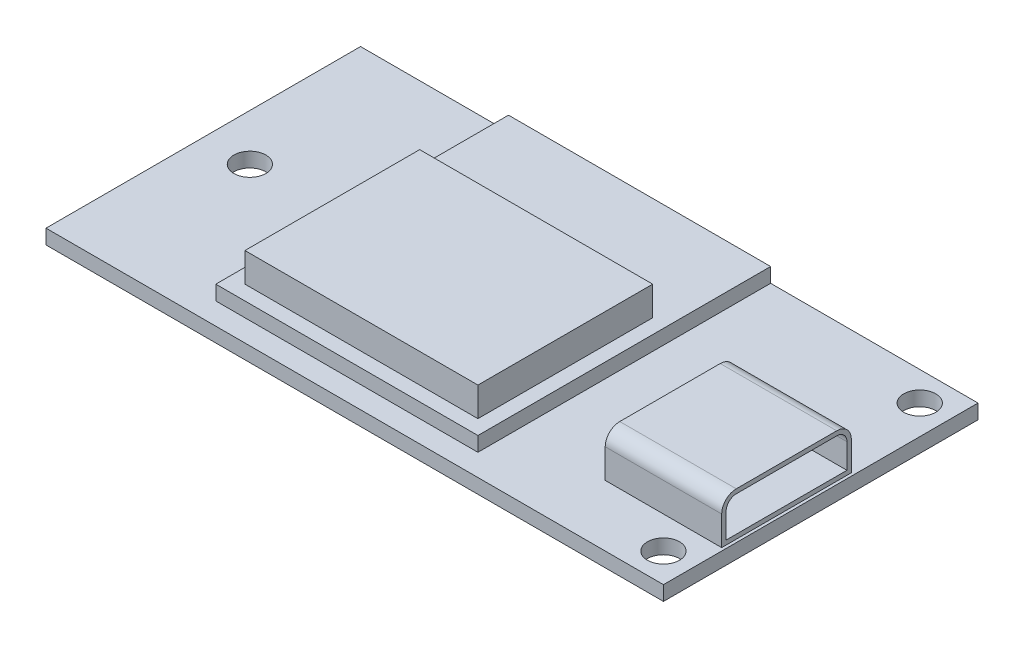
SolidWorks part; units mm, degrees
ref_plane "前视基准面" through (0, 0, 0) normal (0, 0, 1) x (1, 0, 0)
ref_plane "上视基准面" through (0, 0, 0) normal (0, 1, 0) x (1, 0, 0)
ref_plane "右视基准面" through (0, 0, 0) normal (1, 0, 0) x (0, 0, -1)
sketch "草图1" plane through (0, 0, 0) normal (0, 1, 0) x (1, 0, 0)
  line L1 (-21.2, 10.8) -> (21.2, 10.8)
  line L2 (-21.2, 10.8) -> (-21.2, -10.8)
  line L3 (-21.2, -10.8) -> (21.2, -10.8)
  line L4 (21.2, 10.8) -> (21.2, -10.8)
  line L5 (-21.2, 10.8) -> (21.2, -10.8) construction
  line L6 (-21.2, -10.8) -> (21.2, 10.8) construction
  circle A0 centre (-18, 0) radius 1.1
  circle A1 centre (19.2, 8.8) radius 1.1
  circle A2 centre (19.2, -8.8) radius 1.1
  point P0 (0, 0)
  dimension "D5" = 2.2
  dimension "D8" = 2.2
  dimension "D11" = 2.2
  dimension "D2" = 17.6
  dimension "D3" = 3.2
  dimension "D4" = 10.8
  dimension "D6" = 2
  dimension "D7" = 2
  dimension "D9" = 2
  dimension "D10" = 2
  dimension "D12" = 37.2
extrude "凸台-拉伸1" add sketch "草图1" along normal blind 1
sketch "草图2" plane through (0, 1, 0) normal (0, 1, 0) x (1, 0, 0)
  line L1 (-11.04, 4.7) -> (6.96, 4.7)
  line L2 (-11.04, 4.7) -> (-11.04, -9.3)
  line L3 (-11.04, -9.3) -> (6.96, -9.3)
  line L4 (21.2, -10.8) -> (21.2, 10.8)
  line L5 (21.2, 10.8) -> (-21.2, 10.8)
  line L6 (-21.2, 10.8) -> (-21.2, -10.8)
  line L7 (-21.2, -10.8) -> (21.2, -10.8)
  line L8 (21.2, -10.8) -> (21.2, 10.8)
  line L9 (21.2, 10.8) -> (-21.2, 10.8)
  line L10 (-21.2, 10.8) -> (-21.2, -10.8)
  line L11 (-21.2, -10.8) -> (21.2, -10.8)
  line L12 (6.96, 4.7) -> (6.96, -9.3)
  line L13 (13, 2.3) -> (21, 2.3)
  line L14 (13, 2.3) -> (13, -6.6)
  line L15 (13, -6.6) -> (21, -6.6)
  line L16 (21, 2.3) -> (21, -6.6)
  line L17 (6.96, 4.7) -> (-11.04, 4.7)
  line L18 (6.96, 4.7) -> (6.96, 10.8)
  line L19 (6.96, 10.8) -> (-11.04, 10.8)
  line L20 (-11.04, 4.7) -> (-11.04, 10.8)
  dimension "D2" = 10.16
  dimension "D3" = 6.1
  dimension "D4" = 18
  dimension "D5" = 14
  dimension "D6" = 4.2
  dimension "D7" = 0.2
  dimension "D8" = 8
  dimension "D9" = 8.9
  dimension "D1" = 0
extrude "凸台-拉伸2" add sketch "草图2" along normal blind 3 contours L12 L1 L2 L3 | L16 L13 L14 L15 region at (-2.04, 1, 2.3) region at (17, 1, 2.15)
fillet "圆角1" radius 1 2 edges at (17, 4, 6.6) (17, 4, -2.3)
extrude "凸台-拉伸3" add sketch "草图2<3>" along normal blind 1 contours L20 L1 L18 L9 region at (-2.04, 1, -7.75)
sketch "草图2<3>" plane through (0, 1, 0) normal (0, 1, 0) x (1, 0, 0) same geometry as "草图2"
sketch "草图3" plane through (21, 0, 0) normal (1, 0, 0) x (0, 0, -1)
  line L0 (1.3, 3.7) -> (-5.6, 3.7)
  line L1 (-6.3, 3) -> (-6.3, 1.3)
  line L2 (-6.3, 1.3) -> (2, 1.3)
  line L3 (2, 1.3) -> (2, 3)
  line L4 (1.3, 4) -> (-5.6, 4)
  line L5 (-6.6, 3) -> (-6.6, 1)
  line L6 (-6.6, 1) -> (2.3, 1)
  line L7 (2.3, 1) -> (2.3, 3)
  line L8 (1.3, 4) -> (-5.6, 4)
  line L9 (-6.6, 3) -> (-6.6, 1)
  line L10 (-6.6, 1) -> (2.3, 1)
  line L11 (2.3, 1) -> (2.3, 3)
  arc A0 (-5.6, 3.7) -> (-6.3, 3) centre (-5.6, 3) ccw
  arc A1 (2, 3) -> (1.3, 3.7) centre (1.3, 3) ccw
  arc A2 (-5.6, 4) -> (-6.6, 3) centre (-5.6, 3) ccw
  arc A3 (2.3, 3) -> (1.3, 4) centre (1.3, 3) ccw
  arc A4 (-5.6, 4) -> (-6.6, 3) centre (-5.6, 3) ccw
  arc A5 (2.3, 3) -> (1.3, 4) centre (1.3, 3) ccw
  dimension "D1" = 0
  dimension "D2" = 0.3
extrude "切除-拉伸1" cut sketch "草图3" against normal offset from surface (7.7 mm away) 0.3 contours L0 A0 L1 L2 L3 A1 up to face at (13, 2.7357, 2.15)
sketch "草图4" plane through (0, 4, 0) normal (0, 1, 0) x (1, 0, 0)
  line L4 (6.96, -9.3) -> (6.96, 4.7)
  line L5 (6.96, 4.7) -> (-11.04, 4.7)
  line L6 (-11.04, 4.7) -> (-11.04, -9.3)
  line L7 (-11.04, -9.3) -> (6.96, -9.3)
  line L8 (6.96, -9.3) -> (6.96, 4.7)
  line L9 (6.96, 4.7) -> (-11.04, 4.7)
  line L10 (-11.04, 4.7) -> (-11.04, -9.3)
  line L11 (-11.04, -9.3) -> (6.96, -9.3)
  dimension "D1" = 0
extrude "切除-拉伸-薄壁1" cut sketch "草图4" against normal up to surface (2 mm away) thin up to face at (-2.04, 2, -7.75) thin type one direction reverse wall 1
